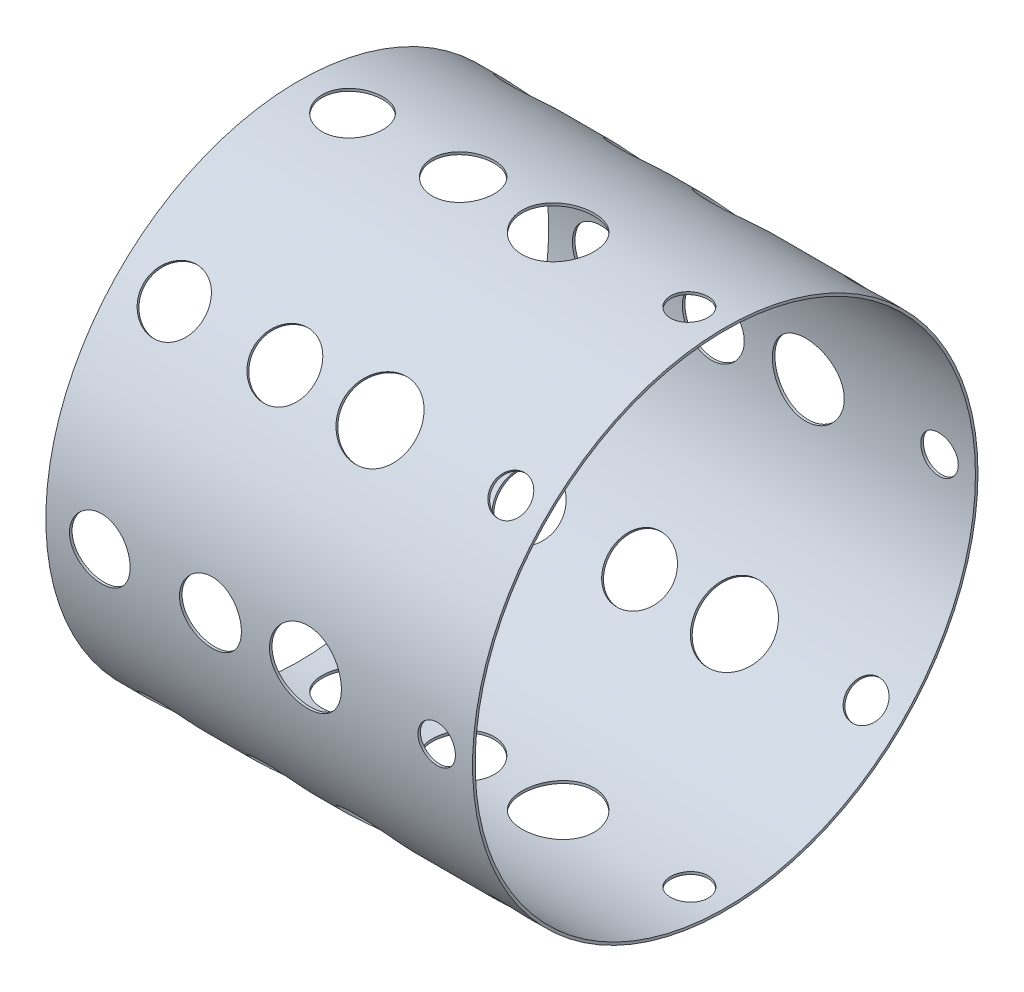
SolidWorks part; units mm, degrees
ref_plane "Front Plane" through (0, 0, 0) normal (0, 0, 1) x (1, 0, 0)
ref_plane "Top Plane" through (0, 0, 0) normal (0, 1, 0) x (1, 0, 0)
ref_plane "Right Plane" through (0, 0, 0) normal (1, 0, 0) x (0, 0, -1)
sketch "Sketch1" plane through (0, 0, 0) normal (1, 0, 0) x (0, 0, -1)
  circle A0 centre (0, 0) radius 59.563
  circle A1 centre (0, 0) radius 60.1701
  dimension "D1" = 119.126
  dimension "D2" = 0.6071
extrude "Boss-Extrude1" add sketch "Sketch1" along normal blind 101.6
sketch "Sketch2" plane through (0, 0, 0) normal (0, 0, 1) x (1, 0, 0)
  line L0 (4.6468, 0) -> (109.4742, 0) construction
sketch "Sketch3" plane through (0, 0, 0) normal (0, 1, 0) x (1, 0, 0)
  line L0 (4.6468, 0) -> (109.4742, 0) construction
  circle A0 centre (12.8558, 0) radius 7.2158
  circle A1 centre (39.1897, 0) radius 7.3646
  circle A2 centre (61.8041, 0) radius 8.5548
  circle A3 centre (93.0477, 0) radius 4.4634
extrude "Cut-Extrude1" cut sketch "Sketch3" against normal through all and the other way through all
pattern_circular "CirPattern1" count 8 over 360 about axis through (4.6468, 0, 0) along (1, 0, 0) of "Cut-Extrude1" reverse direction yes
